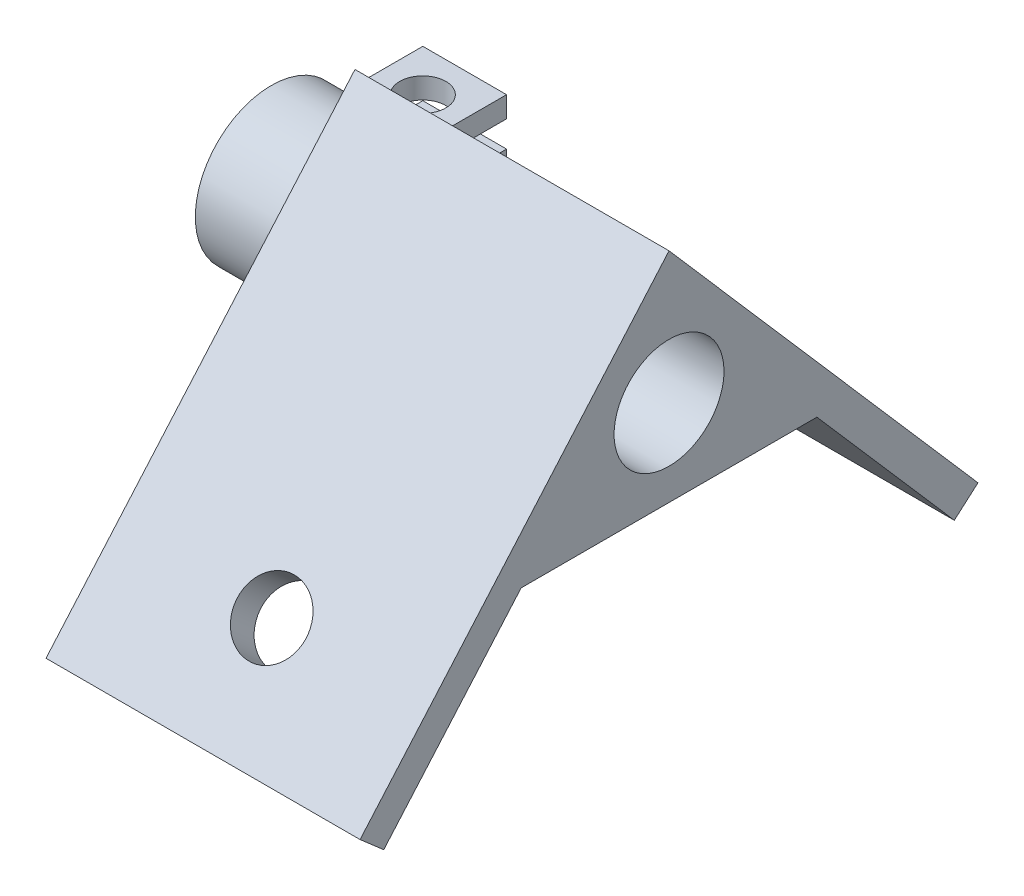
SolidWorks part; units mm, degrees
material "PLA Black"
ref_plane "Front" through (0, 0, 0) normal (0, 0, 1) x (1, 0, 0)
ref_plane "Top" through (0, 0, 0) normal (0, 1, 0) x (1, 0, 0)
ref_plane "Right" through (0, 0, 0) normal (1, 0, 0) x (0, 0, -1)
sketch "Sketch1" plane through (0, 0, 0) normal (1, 0, 0) x (0, 0, -1)
  line L0 (0, 12.5751) -> (-29.5132, -21.376)
  line L1 (-29.5132, -21.376) -> (-27.2491, -23.3442)
  line L2 (-27.2491, -23.3442) -> (-14.1279, -8.25)
  line L3 (-14.1279, -8.25) -> (14.1279, -8.25)
  line L4 (0, 31.2499) -> (0, -31.1028) construction
  line L5 (27.2491, -23.3442) -> (14.1279, -8.25)
  line L6 (0, 12.5751) -> (29.5132, -21.376)
  line L7 (29.5132, -21.376) -> (27.2491, -23.3442)
  circle A0 centre (0, 0) radius 5.25
  dimension "D1" = 10.5
  dimension "D4" = 3
  dimension "D2" = 41
  dimension "D3" = 3
  dimension "D5" = 3
  dimension "D6" = 20
extrude "Boss-Extrude1" add sketch "Sketch1" along normal mid plane 30
hole_wizard "M6 Clearance Hole1" positions "Sketch3" profile "Sketch4" hole size "M6" standard "DIN" end condition through all
sketch "Sketch3" plane through (0, 3.4443, 3.9622) normal (0, -0.6561, -0.7547) x (-1, 0, 0)
  line L0 (-34.564, -25.4951) -> (6.8322, -25.4951) construction
  line L2 (0, -15.4951) -> (0, -35.4951) construction
  line L3 (-15, -15.4951) -> (15, -15.4951) construction
  line L4 (-15, -35.4951) -> (15, -35.4951) construction
  point P0 (0, -25.4951)
sketch "Sketch4" plane through (0, -15.7971, 20.6885) normal (1, 0, 0) x (0, 0.7547, -0.6561)
  line L0 (0, 0) -> (0, 25.2739)
  line L1 (0, 25.2739) -> (3.3, 25.2739)
  line L2 (3.3, 25.2739) -> (3.3, 0)
  line L5 (3.3, 0) -> (0, 0)
  line L11 (0, -6.35) -> (0, 107.95) construction
  dimension "Thru Hole Dia." = 6.6
  dimension "Thru Hole Depth" = 25.2739
mirror "Mirror1" about plane through (0, 0, 0) normal (0, 0, 1) of "M6 Clearance Hole1"
sketch "Sketch5" plane through (-15, 0, 0) normal (-1, 0, 0) x (0, 0, 1)
  line L0 (-5.099, 1.25) -> (-14.4807, 1.25)
  line L1 (-14.4807, 1.25) -> (-14.4807, 3.25)
  line L2 (-14.4807, 3.25) -> (-6.4807, 3.25)
  line L3 (0, 0) -> (-16.2155, 0) construction
  line L4 (-6.4807, -3.25) -> (-6.4807, -10.25)
  line L5 (-14.4807, -1.25) -> (-14.4807, -10.25)
  line L6 (-5.099, -1.25) -> (-14.4807, -1.25)
  line L7 (-6.4807, -10.25) -> (-14.4807, -10.25)
  circle A0 centre (0, 0) radius 5.25 construction
  arc A1 (-6.4807, 3.25) -> (-6.4807, -3.25) centre (0, 0) cw
  arc A2 (-5.099, 1.25) -> (-5.099, -1.25) centre (0, 0) cw
  dimension "D1" = 2
  dimension "D2" = 8
  dimension "D3" = 2.5
  dimension "D4" = 2
  dimension "D5" = 9
extrude "Boss-Extrude2" add sketch "Sketch5" along normal blind 8
sketch "Sketch6" plane through (0, 3.25, 0) normal (0, 1, 0) x (1, 0, 0)
  line L0 (-19, 14.4807) -> (-19, 6.4807) construction
  line L1 (-23, 14.4807) -> (-15, 14.4807) construction
  line L2 (-23, 6.4807) -> (-15, 6.4807) construction
  circle A0 centre (-19, 10.4807) radius 2.2
  dimension "D1" = 4.4
extrude "Cut-Extrude1" cut sketch "Sketch6" against normal through all
